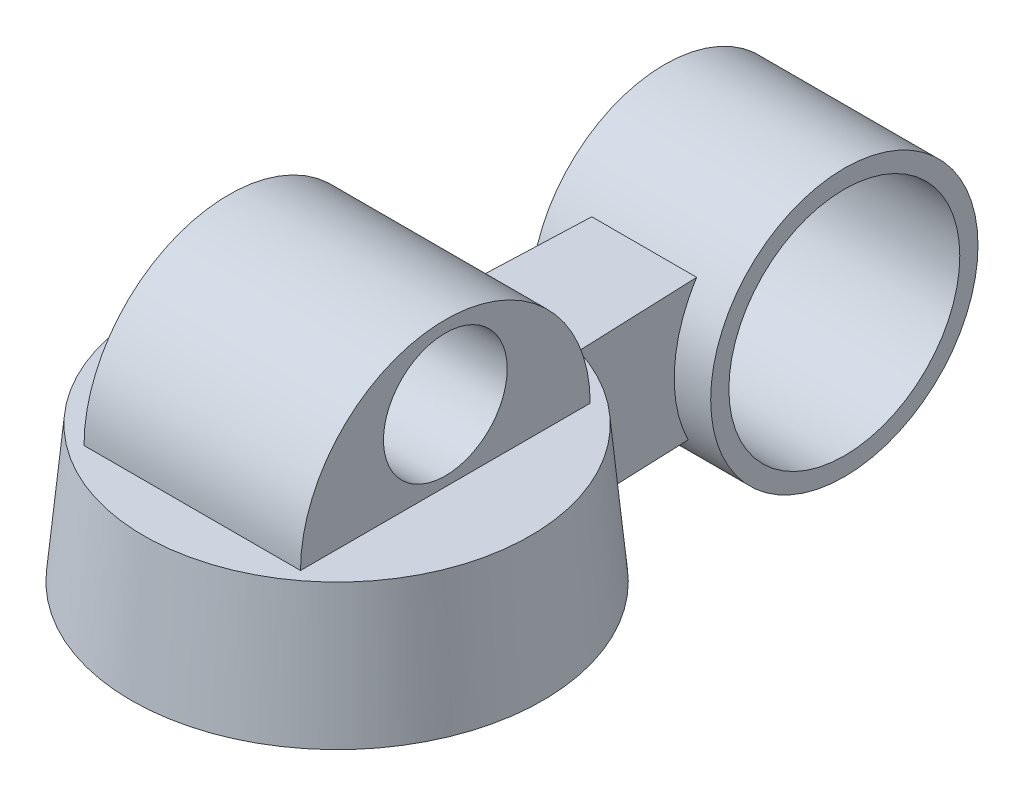
SolidWorks part; units mm, degrees
ref_plane "Front Plane" through (0, 0, 0) normal (0, 0, 1) x (1, 0, 0)
ref_plane "Top Plane" through (0, 0, 0) normal (0, 1, 0) x (1, 0, 0)
ref_plane "Right Plane" through (0, 0, 0) normal (1, 0, 0) x (0, 0, -1)
sketch "Sketch1" plane through (0, 0, 0) normal (0, 0, 1) x (1, 0, 0)
  line L0 (-40.3145, 0) -> (-46.3804, 0)
  line L1 (-46.3804, 0) -> (-43.5102, 30.6558)
  line L2 (-43.5102, 30.6558) -> (0, 30.6558)
  line L3 (0, 0) -> (0, -34.4351) construction
  line L4 (0, 11.7018) -> (0, 30.6558)
  line L5 (0, 11.7018) -> (-40.3145, 11.7018)
  line L6 (-40.3145, 11.7018) -> (-40.3145, 0)
revolve "Revolve1" add sketch "Sketch1" angle 360 about L3
sketch "Sketch2" plane through (0, 0, 0) normal (1, 0, 0) x (0, 0, -1)
  line L0 (0, 30.6558) -> (-32.6253, 30.6558)
  line L1 (43.5102, 30.6558) -> (-43.5102, 30.6558) construction
  line L2 (0, 30.6558) -> (32.6253, 30.6558)
  arc A0 (-32.6253, 30.6558) -> (32.6253, 30.6558) centre (0, 30.6558) cw
  circle A1 centre (0, 46.7345) radius 13.9352
  dimension "D1" = 32.6253
  dimension "D3" = 27.8704
  dimension "D2" = 16.0787
extrude "Boss-Extrude1" add sketch "Sketch2" along normal blind 24.3806 and the other way blind 24.3806
sketch "Sketch4" plane through (0, 0, 0) normal (0, 1, 0) x (1, 0, 0)
  line L0 (-12.7279, 45.6093) -> (12.7279, 45.6093) construction
  line L1 (12.7279, 45.6093) -> (10.7808, 95.9546)
  line L2 (10.7808, 95.9546) -> (-10.7808, 95.9546)
  line L3 (-10.7808, 95.9546) -> (-12.7279, 45.6093)
  line L4 (0, 0) -> (0, 60.8523) construction
  line L5 (-12.7279, 45.6093) -> (-12.9276, 40.4457)
  line L6 (-12.9276, 40.4457) -> (12.9276, 40.4457)
  line L7 (12.9276, 40.4457) -> (12.7279, 45.6093)
  point P5 (0, 95.9546)
  point P9 (0, 45.6093)
  dimension "D1" = 21.5616
  dimension "D2" = 25.4559
  dimension "D3" = 50.3453
  dimension "D4" = 45.6093
extrude "Boss-Extrude2" add sketch "Sketch4" along normal blind 30.6558
sketch "Sketch5" plane through (0, 0, 0) normal (1, 0, 0) x (0, 0, -1)
  circle A0 centre (94.0135, 13.638) radius 30.1061
  dimension "D1" = 60.2122
extrude "Boss-Extrude3" add sketch "Sketch5" along normal blind 20.2366 and the other way blind 20.2366
sketch "Sketch6" plane through (20.2366, 0, 0) normal (1, 0, 0) x (0, 0, -1)
  circle A0 centre (94.0135, 13.638) radius 26.0046
  dimension "D1" = 52.0093
extrude "Cut-Extrude1" cut sketch "Sketch6" against normal through all
